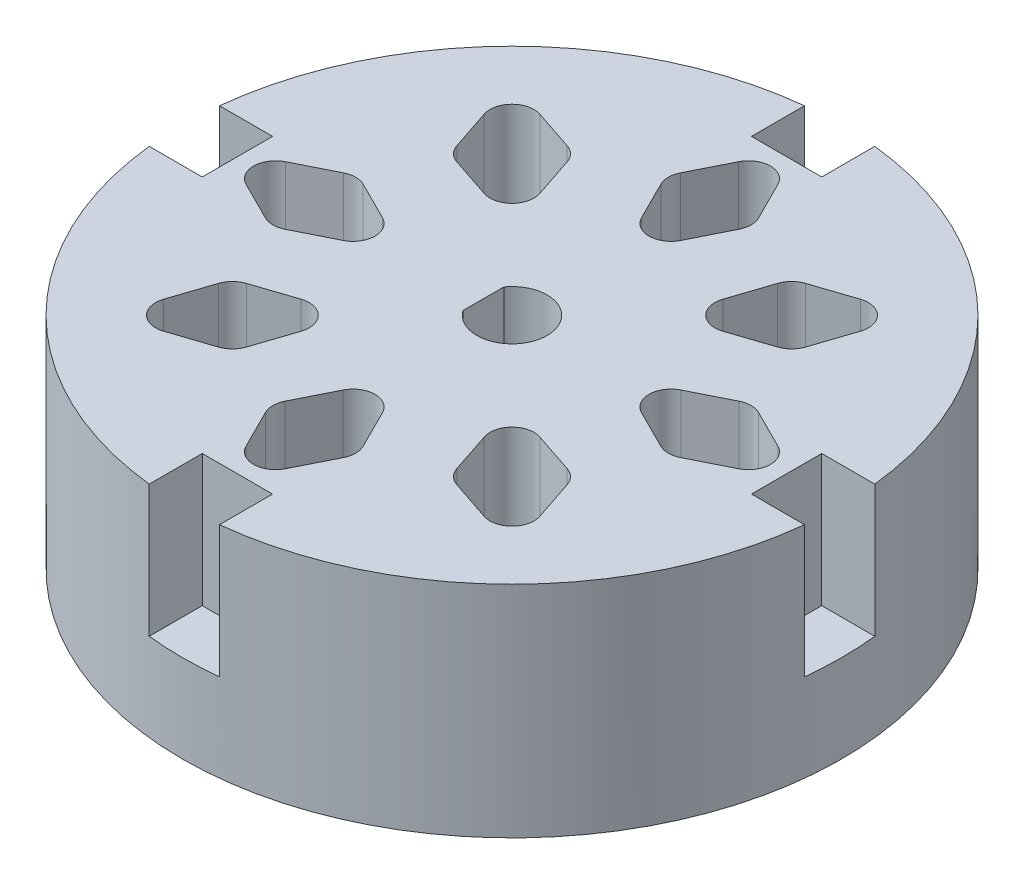
SolidWorks part; units mm, degrees
material "PET"
ref_plane "Спереди" through (0, 0, 0) normal (0, 0, 1) x (1, 0, 0)
ref_plane "Сверху" through (0, 0, 0) normal (0, 1, 0) x (1, 0, 0)
ref_plane "Справа" through (0, 0, 0) normal (1, 0, 0) x (0, 0, -1)
sketch "Эскиз1" plane through (0, 0, 0) normal (0, 1, 0) x (1, 0, 0)
  circle A0 centre (0, 0) radius 4
  circle A1 centre (0, 0) radius 15
  dimension "D1" = 8
  dimension "D2" = 30
extrude "Бобышка-Вытянуть1" add sketch "Эскиз1" along normal blind 10
sketch "Эскиз4" plane through (0, 0, 0) normal (0, -1, 0) x (1, 0, 0)
  circle A16 centre (0, 0) radius 15
  circle A32 centre (0, 0) radius 15
  dimension "D1" = 0
extrude "Бобышка-Вытянуть2" add sketch "Эскиз4" against normal blind 6
sketch "Эскиз5" plane through (0, 6, 0) normal (0, 1, 0) x (1, 0, 0)
  circle A0 centre (0, 0) radius 1.6
  dimension "D1" = 3.2
extrude "Вырез-Вытянуть2" cut sketch "Эскиз5" against normal through all both and the other way through all
sketch "Эскиз6" plane through (0, 0, 0) normal (0, -1, 0) x (1, 0, 0)
  line L0 (0, 0) -> (-5, 0) construction
  line L1 (-6.7889, 0.8944) -> (-8.5528, 1.7764)
  line L2 (-9.4472, 1.7764) -> (-11.2111, 0.8944)
  line L3 (-11.2111, -0.8944) -> (-9.4472, -1.7764)
  line L4 (-8.5528, -1.7764) -> (-6.7889, -0.8944)
  line L5 (-13, 0) -> (-5, 0) construction
  line L6 (-9, 2) -> (-9, -2) construction
  line L7 (-4.168, 5.4329) -> (-4.7916, 7.3038)
  line L8 (-5.4241, 7.9363) -> (-7.295, 8.5599)
  line L9 (-8.5599, 7.295) -> (-7.9363, 5.4241)
  line L10 (-7.3038, 4.7916) -> (-5.4329, 4.168)
  line L11 (0, 0) -> (-3.5355, 3.5355) construction
  line L12 (-9.1924, 9.1924) -> (-3.5355, 3.5355) construction
  line L13 (-4.9497, 7.7782) -> (-7.7782, 4.9497) construction
  line L14 (0.8944, 6.7889) -> (1.7764, 8.5528)
  line L15 (1.7764, 9.4472) -> (0.8944, 11.2111)
  line L16 (-0.8944, 11.2111) -> (-1.7764, 9.4472)
  line L17 (-1.7764, 8.5528) -> (-0.8944, 6.7889)
  line L18 (0, 0) -> (0, 5) construction
  line L19 (0, 13) -> (0, 5) construction
  line L20 (2, 9) -> (-2, 9) construction
  line L21 (5.4329, 4.168) -> (7.3038, 4.7916)
  line L22 (7.9363, 5.4241) -> (8.5599, 7.295)
  line L23 (7.295, 8.5599) -> (5.4241, 7.9363)
  line L24 (4.7916, 7.3038) -> (4.168, 5.4329)
  line L25 (0, 0) -> (3.5355, 3.5355) construction
  line L26 (9.1924, 9.1924) -> (3.5355, 3.5355) construction
  line L27 (7.7782, 4.9497) -> (4.9497, 7.7782) construction
  line L28 (6.7889, -0.8944) -> (8.5528, -1.7764)
  line L29 (9.4472, -1.7764) -> (11.2111, -0.8944)
  line L30 (11.2111, 0.8944) -> (9.4472, 1.7764)
  line L31 (8.5528, 1.7764) -> (6.7889, 0.8944)
  line L32 (0, 0) -> (5, 0) construction
  line L33 (13, 0) -> (5, 0) construction
  line L34 (9, -2) -> (9, 2) construction
  line L35 (4.168, -5.4329) -> (4.7916, -7.3038)
  line L36 (5.4241, -7.9363) -> (7.295, -8.5599)
  line L37 (8.5599, -7.295) -> (7.9363, -5.4241)
  line L38 (7.3038, -4.7916) -> (5.4329, -4.168)
  line L39 (0, 0) -> (3.5355, -3.5355) construction
  line L40 (9.1924, -9.1924) -> (3.5355, -3.5355) construction
  line L41 (4.9497, -7.7782) -> (7.7782, -4.9497) construction
  line L42 (-0.8944, -6.7889) -> (-1.7764, -8.5528)
  line L43 (-1.7764, -9.4472) -> (-0.8944, -11.2111)
  line L44 (0.8944, -11.2111) -> (1.7764, -9.4472)
  line L45 (1.7764, -8.5528) -> (0.8944, -6.7889)
  line L46 (0, 0) -> (0, -5) construction
  line L47 (0, -13) -> (0, -5) construction
  line L48 (-2, -9) -> (2, -9) construction
  line L49 (-5.4329, -4.168) -> (-7.3038, -4.7916)
  line L50 (-7.9363, -5.4241) -> (-8.5599, -7.295)
  line L51 (-7.295, -8.5599) -> (-5.4241, -7.9363)
  line L52 (-4.7916, -7.3038) -> (-4.168, -5.4329)
  line L53 (0, 0) -> (-3.5355, -3.5355) construction
  line L54 (-9.1924, -9.1924) -> (-3.5355, -3.5355) construction
  line L55 (-7.7782, -4.9497) -> (-4.9497, -7.7782) construction
  arc A0 (-9.4472, -1.7764) -> (-8.5528, -1.7764) centre (-9, -0.882) ccw
  arc A1 (-6.7889, -0.8944) -> (-6.7889, 0.8944) centre (-7.2361, 0) ccw
  arc A2 (-8.5528, 1.7764) -> (-9.4472, 1.7764) centre (-9, 0.882) ccw
  arc A3 (-11.2111, 0.8944) -> (-11.2111, -0.8944) centre (-10.7639, 0) ccw
  arc A4 (-7.9363, 5.4241) -> (-7.3038, 4.7916) centre (-6.9876, 5.7403) ccw
  arc A5 (-5.4329, 4.168) -> (-4.168, 5.4329) centre (-5.1167, 5.1167) ccw
  arc A6 (-4.7916, 7.3038) -> (-5.4241, 7.9363) centre (-5.7403, 6.9876) ccw
  arc A7 (-7.295, 8.5599) -> (-8.5599, 7.295) centre (-7.6112, 7.6112) ccw
  arc A8 (-1.7764, 9.4472) -> (-1.7764, 8.5528) centre (-0.882, 9) ccw
  arc A9 (-0.8944, 6.7889) -> (0.8944, 6.7889) centre (0, 7.2361) ccw
  arc A10 (1.7764, 8.5528) -> (1.7764, 9.4472) centre (0.882, 9) ccw
  arc A11 (0.8944, 11.2111) -> (-0.8944, 11.2111) centre (0, 10.7639) ccw
  arc A12 (5.4241, 7.9363) -> (4.7916, 7.3038) centre (5.7403, 6.9876) ccw
  arc A13 (4.168, 5.4329) -> (5.4329, 4.168) centre (5.1167, 5.1167) ccw
  arc A14 (7.3038, 4.7916) -> (7.9363, 5.4241) centre (6.9876, 5.7403) ccw
  arc A15 (8.5599, 7.295) -> (7.295, 8.5599) centre (7.6112, 7.6112) ccw
  arc A16 (9.4472, 1.7764) -> (8.5528, 1.7764) centre (9, 0.882) ccw
  arc A17 (6.7889, 0.8944) -> (6.7889, -0.8944) centre (7.2361, 0) ccw
  arc A18 (8.5528, -1.7764) -> (9.4472, -1.7764) centre (9, -0.882) ccw
  arc A19 (11.2111, -0.8944) -> (11.2111, 0.8944) centre (10.7639, 0) ccw
  arc A20 (7.9363, -5.4241) -> (7.3038, -4.7916) centre (6.9876, -5.7403) ccw
  arc A21 (5.4329, -4.168) -> (4.168, -5.4329) centre (5.1167, -5.1167) ccw
  arc A22 (4.7916, -7.3038) -> (5.4241, -7.9363) centre (5.7403, -6.9876) ccw
  arc A23 (7.295, -8.5599) -> (8.5599, -7.295) centre (7.6112, -7.6112) ccw
  arc A24 (1.7764, -9.4472) -> (1.7764, -8.5528) centre (0.882, -9) ccw
  arc A25 (0.8944, -6.7889) -> (-0.8944, -6.7889) centre (0, -7.2361) ccw
  arc A26 (-1.7764, -8.5528) -> (-1.7764, -9.4472) centre (-0.882, -9) ccw
  arc A27 (-0.8944, -11.2111) -> (0.8944, -11.2111) centre (0, -10.7639) ccw
  arc A28 (-5.4241, -7.9363) -> (-4.7916, -7.3038) centre (-5.7403, -6.9876) ccw
  arc A29 (-4.168, -5.4329) -> (-5.4329, -4.168) centre (-5.1167, -5.1167) ccw
  arc A30 (-7.3038, -4.7916) -> (-7.9363, -5.4241) centre (-6.9876, -5.7403) ccw
  arc A31 (-8.5599, -7.295) -> (-7.295, -8.5599) centre (-7.6112, -7.6112) ccw
  point P3 (-9, 0)
  point P21 (0, -9)
  point P23 (-6.364, 6.364)
  point P40 (0, 9)
  point P57 (6.364, 6.364)
  point P74 (9, 0)
  point P91 (6.364, -6.364)
  point P107 (0, 0)
  point P123 (-6.364, -6.364)
  dimension "D4" = 1
  dimension "D1" = 4
  dimension "D2" = 8
  dimension "D3" = 5
  dimension "D5" = 8
extrude "Вырез-Вытянуть3" cut sketch "Эскиз6" against normal through all both and the other way through all
sketch "Эскиз8" plane through (0, 10, 0) normal (0, 1, 0) x (1, 0, 0)
  line L0 (0, 0) -> (-15, 0) construction
  line L1 (1.6, 12.5) -> (1.6, 17.5)
  line L2 (-12.5, 1.6) -> (-17.5, 1.6)
  line L3 (-12.5, 1.6) -> (-12.5, -1.6)
  line L4 (-12.5, -1.6) -> (-17.5, -1.6)
  line L5 (-17.5, 1.6) -> (-17.5, -1.6)
  line L6 (-12.5, 1.6) -> (-17.5, -1.6) construction
  line L7 (-12.5, -1.6) -> (-17.5, 1.6) construction
  line L8 (1.6, 12.5) -> (-1.6, 12.5)
  line L9 (-1.6, 12.5) -> (-1.6, 17.5)
  line L10 (1.6, 17.5) -> (-1.6, 17.5)
  line L11 (0, 0) -> (0, 15) construction
  line L12 (1.6, 12.5) -> (-1.6, 17.5) construction
  line L13 (-1.6, 12.5) -> (1.6, 17.5) construction
  line L14 (12.5, -1.6) -> (17.5, -1.6)
  line L15 (12.5, -1.6) -> (12.5, 1.6)
  line L16 (12.5, 1.6) -> (17.5, 1.6)
  line L17 (17.5, -1.6) -> (17.5, 1.6)
  line L18 (0, 0) -> (15, 0) construction
  line L19 (12.5, -1.6) -> (17.5, 1.6) construction
  line L20 (12.5, 1.6) -> (17.5, -1.6) construction
  line L21 (-1.6, -12.5) -> (-1.6, -17.5)
  line L22 (-1.6, -12.5) -> (1.6, -12.5)
  line L23 (1.6, -12.5) -> (1.6, -17.5)
  line L24 (-1.6, -17.5) -> (1.6, -17.5)
  line L25 (0, 0) -> (0, -15) construction
  line L26 (-1.6, -12.5) -> (1.6, -17.5) construction
  line L27 (1.6, -12.5) -> (-1.6, -17.5) construction
  circle A0 centre (0, 0) radius 15 construction
  point P28 (0, 0)
  dimension "D1" = 3.2
  dimension "D2" = 5
  dimension "D3" = 4
extrude "Вырез-Вытянуть4" cut sketch "Эскиз8" against normal blind 6
sketch "Эскиз9" plane through (0, 0, 0) normal (0, -1, 0) x (1, 0, 0)
  circle A0 centre (0, 0) radius 3
  dimension "D1" = 6
extrude "Вырез-Вытянуть5" cut sketch "Эскиз9" against normal blind 2
sketch "Эскиз11" plane through (0, 6, 0) normal (0, 1, 0) x (1, 0, 0)
  line L0 (-1.3, 0.9327) -> (-1.3, -0.9327)
  arc A0 (-1.3, -0.9327) -> (-1.3, 0.9327) centre (0, 0) ccw
  circle A2 centre (0, 0) radius 4
  circle A3 centre (0, 0) radius 4
  dimension "D1" = 3.2
  dimension "D2" = 1.3
  dimension "D3" = 0
extrude "Бобышка-Вытянуть3" add sketch "Эскиз11" along normal up to surface (4 mm away) up to face at (0, 10, 0)
sketch "Эскиз12" plane through (0, 2, 0) normal (0, -1, 0) x (1, 0, 0)
  circle A1 centre (0, 0) radius 3
  circle A2 centre (0, 0) radius 3
  dimension "D1" = 0
extrude "Бобышка-Вытянуть4" add sketch "Эскиз12" along normal up to surface (2 mm away) up to face at (0, 0, -3)
sketch "Эскиз13" plane through (0, 2, 0) normal (0, 1, 0) x (1, 0, 0)
  circle A1 centre (0, 0) radius 1.6
  circle A2 centre (0, 0) radius 1.6
  dimension "D1" = 0
extrude "Бобышка-Вытянуть5" add sketch "Эскиз13" along normal blind 2
